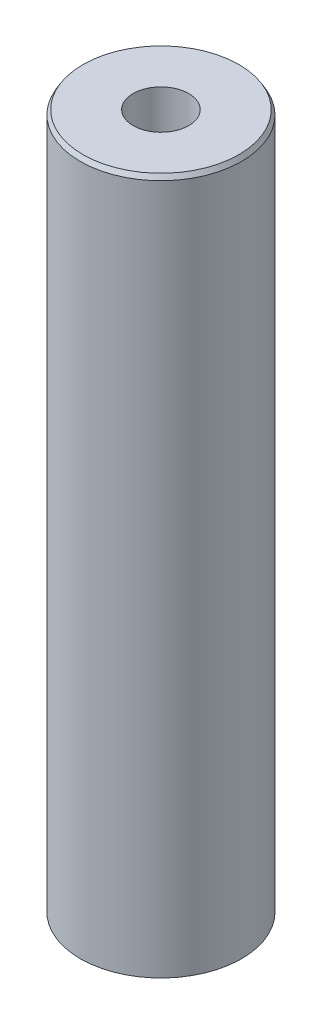
SolidWorks part; units mm, degrees
ref_plane "Front Plane" through (0, 0, 0) normal (0, 0, 1) x (1, 0, 0)
ref_plane "Top Plane" through (0, 0, 0) normal (0, 1, 0) x (1, 0, 0)
ref_plane "Right Plane" through (0, 0, 0) normal (1, 0, 0) x (0, 0, -1)
sketch "Sketch1" plane through (0, 0, 0) normal (0, 1, 0) x (1, 0, 0)
  circle A0 centre (0, 0) radius 52.5
  dimension "SHAFT_OD" = 105
extrude "Boss-Extrude1" add sketch "Sketch1" along normal blind 454.0846
sketch "Sketch2" plane through (0, 0, 0) normal (0, 1, 0) x (1, 0, 0)
  circle A0 centre (0, 0) radius 18.1012
  dimension "BORE_D" = 36.2024
extrude "Cut-Extrude1" cut sketch "Sketch2" along normal through all
chamfer "Chamfer1" distance 2.9925 angle 30 2 edges at (0, 454.0846, 52.5) (0, 0, 52.5) first distance on face at (0, 454.0846, 52.5) first distance on face at (0, 0, 18.1012)
